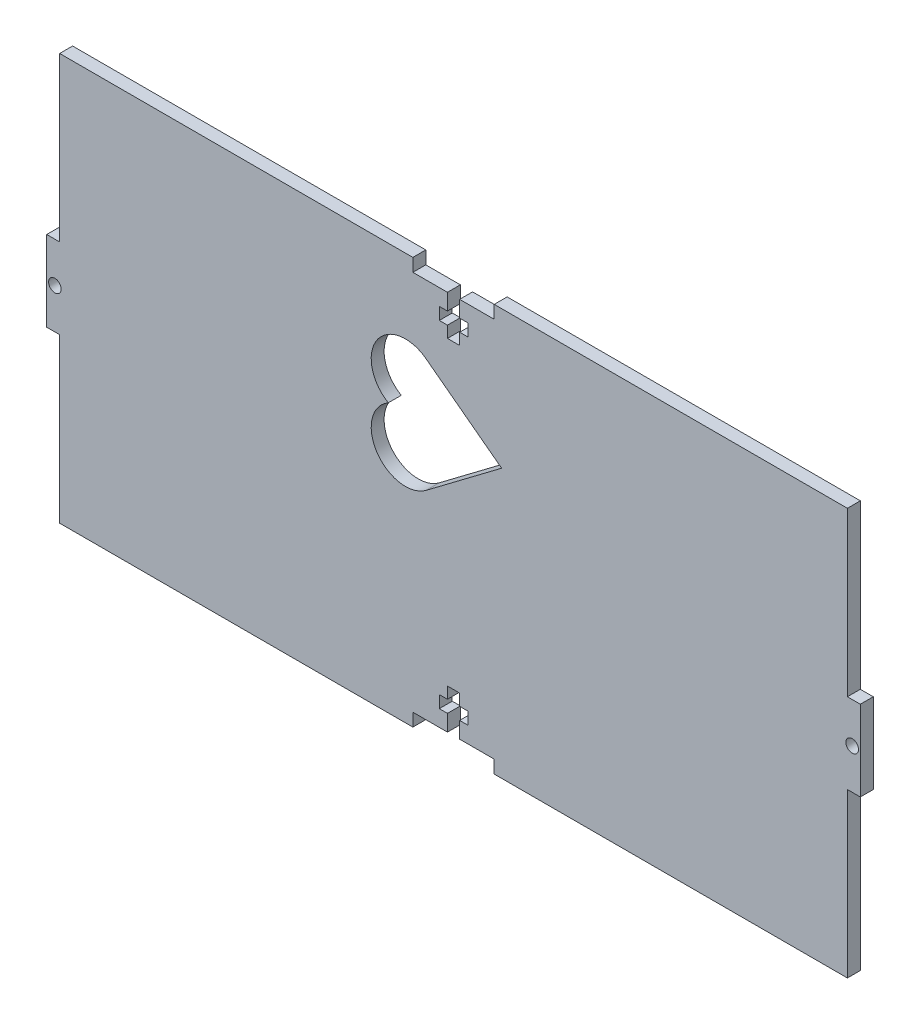
SolidWorks part; units mm, degrees
ref_plane "Front Plane" through (0, 0, 0) normal (0, 0, 1) x (1, 0, 0)
ref_plane "Top Plane" through (0, 0, 0) normal (0, 1, 0) x (1, 0, 0)
ref_plane "Right Plane" through (0, 0, 0) normal (1, 0, 0) x (0, 0, -1)
sketch "Sketch1" plane through (0, 0, 0) normal (0, 0, 1) x (1, 0, 0)
  line L0 (0, 40) -> (0, -40) construction
  line L5 (-100, -50) -> (100, 50) construction
  line L6 (-100, 50) -> (100, -50) construction
  line L7 (-100, 0) -> (100, 0) construction
  line L32 (-100, 50) -> (100, 50)
  line L35 (100, 50) -> (100, -50)
  line L36 (100, -50) -> (-100, -50)
  line L37 (-100, -50) -> (-100, 50)
  point P0 (0, 0)
  dimension "D1" = 200
  dimension "D2" = 100
extrude "Boss-Extrude2" add sketch "Sketch1" along normal blind 3.18
sketch "Sketch2" plane through (0, 0, 3.18) normal (0, 0, 1) x (1, 0, 0)
  line L0 (0, -50) -> (0, 50) construction
  line L1 (-123.0225, 0) -> (147.0753, 0) construction
  line L2 (100, 50) -> (-100, 50) construction
  line L4 (-10, 50) -> (-10, 46.82)
  line L5 (-10, 46.82) -> (-1.5, 46.82)
  line L6 (10, 50) -> (10, 46.82)
  line L7 (1.5, 46.82) -> (10, 46.82)
  line L9 (-1.5, 46.82) -> (-1.5, 42.82)
  line L10 (-1.5, 37) -> (1.5, 37)
  line L11 (1.5, 46.82) -> (1.5, 42.82)
  line L12 (-3.5, 42.82) -> (-1.5, 42.82)
  line L13 (-3.5, 42.82) -> (-3.5, 39.82)
  line L14 (-3.5, 39.82) -> (-1.5, 39.82)
  line L15 (3.5, 42.82) -> (3.5, 39.82)
  line L16 (1.5, 42.82) -> (3.5, 42.82)
  line L17 (-1.5, 39.82) -> (-1.5, 37)
  line L18 (1.5, 39.82) -> (1.5, 37)
  line L19 (1.5, 39.82) -> (3.5, 39.82)
  line L20 (-10, 50) -> (10, 50)
  line L21 (-100, -50) -> (100, -50) construction
  line L22 (-100, 50) -> (-100, -50) construction
  line L23 (-100, 9.875) -> (-96.82, 9.875)
  line L24 (-100, 9.875) -> (-100, 50)
  line L25 (-100, 50) -> (-96.82, 50)
  line L26 (-96.82, 9.875) -> (-96.82, 50)
  line L28 (-100, -9.875) -> (-96.82, -9.875)
  line L29 (-100, -9.875) -> (-100, -50)
  line L30 (-100, -50) -> (-96.82, -50)
  line L31 (-96.82, -9.875) -> (-96.82, -50)
  circle A0 centre (-98, 0) radius 1.55
  dimension "D11" = 3.1
  dimension "D12" = 2
  dimension "D1" = 4
  dimension "D2" = 3
  dimension "D3" = 3
  dimension "D4" = 20
  dimension "D5" = 7
  dimension "D6" = 3.18
  dimension "D7" = 13
  dimension "D8" = 19.75
  dimension "D9" = 3.18
  dimension "D10" = 3.18
extrude "Cut-Extrude1" cut sketch "Sketch2" against normal through all
mirror "Mirror1" about plane through (0, 0, 0) normal (0, 1, 0) of "Cut-Extrude1"
mirror "Mirror2" about plane through (0, 0, 0) normal (1, 0, 0) of "Cut-Extrude1"
sketch "Sketch3" plane through (0, 0, 3.18) normal (0, 0, 1) x (1, 0, 0)
  line L0 (-109.6243, 0) -> (118.6922, 0) construction
  line L1 (0, -53.5977) -> (0, 69.4665) construction
  line L2 (-109.6243, 16.0307) -> (113.5106, 16.0307) construction
  line L3 (11.8206, 16.0307) -> (-6.7588, 30.0396)
  line L4 (11.8206, 16.0307) -> (-6.7588, 2.0219)
  arc A0 (-6.7588, 30.0396) -> (-16.0307, 16.0307) centre (-11.8253, 23.3201) ccw
  arc A1 (-6.7588, 2.0219) -> (-16.0307, 16.0307) centre (-11.8253, 8.7413) cw
  point P7 (-13.4399, 16.0307)
extrude "Cut-Extrude2" cut sketch "Sketch3" against normal through all
